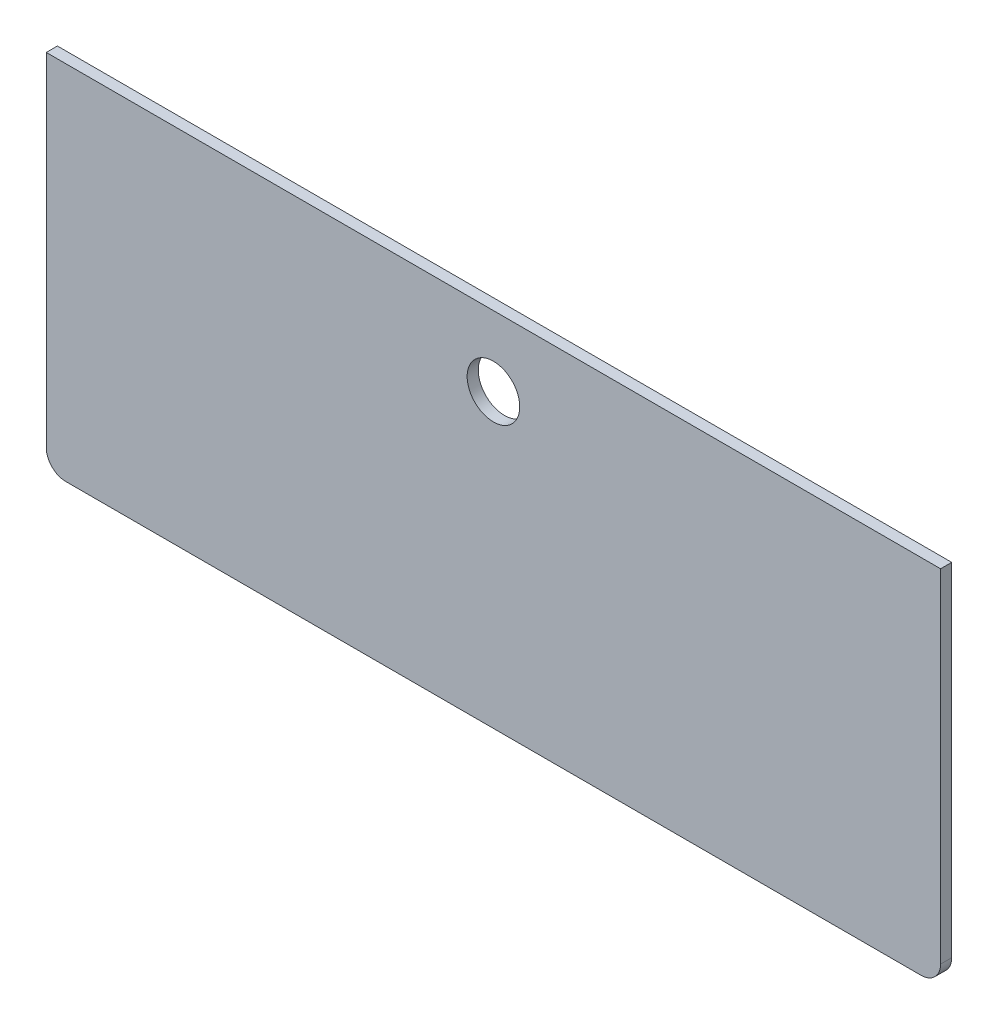
SolidWorks part; units mm, degrees
material "5052-H32"
ref_plane "Front Plane" through (0, 0, 0) normal (0, 0, 1) x (1, 0, 0)
ref_plane "Top Plane" through (0, 0, 0) normal (0, 1, 0) x (1, 0, 0)
ref_plane "Right Plane" through (0, 0, 0) normal (1, 0, 0) x (0, 0, -1)
sketch "Sketch1" plane through (0, 0, 0) normal (0, 0, 1) x (1, 0, 0)
  line L0 (-151.7654, 27.1868) -> (-151.7654, -75.9882)
  line L1 (-151.7654, -75.9882) -> (103.2346, -75.9882)
  line L2 (103.2346, -75.9882) -> (103.2346, 27.1868)
  line L3 (103.2346, 27.1868) -> (-151.7654, 27.1868)
  line L4 (-24.2654, 27.1868) -> (-24.2654, 7.1868) construction
  circle A0 centre (-24.2654, 7.1868) radius 7.5
  dimension "D4" = 15
  dimension "D1" = 103.175
  dimension "D2" = 255
  dimension "D3" = 20
extrude "Boss-Extrude1" add sketch "Sketch1" along normal blind 3.175
fillet "Fillet1" radius 5.5562 2 edges at (-151.7654, -75.9882, 1.5875) (103.2346, -75.9882, 1.5875)
equation "\"L\"= 410mm"
equation "\"W\"= 255mm"
equation "\"H\"= 110mm"
equation "\"Compartment Width\"= 80"
equation "\"T\"= 4.7625 * 2 / 3mm"
equation "\"Inside Fillet Radius\"= 5.55625mm"
equation "\"D1@Boss-Extrude1\"=\"T\""
equation "\"D1@Fillet1\"=\"Inside Fillet Radius\""
equation "\"Hole\"=15mm"
equation "\"D4@Sketch1\"=\"Hole\""
equation "\"D2@Sketch1\"=\"W\""
equation "\"D1@Sketch1\"=\"H\"+\"T\"-10"
equation "\"Offset\"= 13mm"
equation "\"Wheel to Wall\"= 43"
